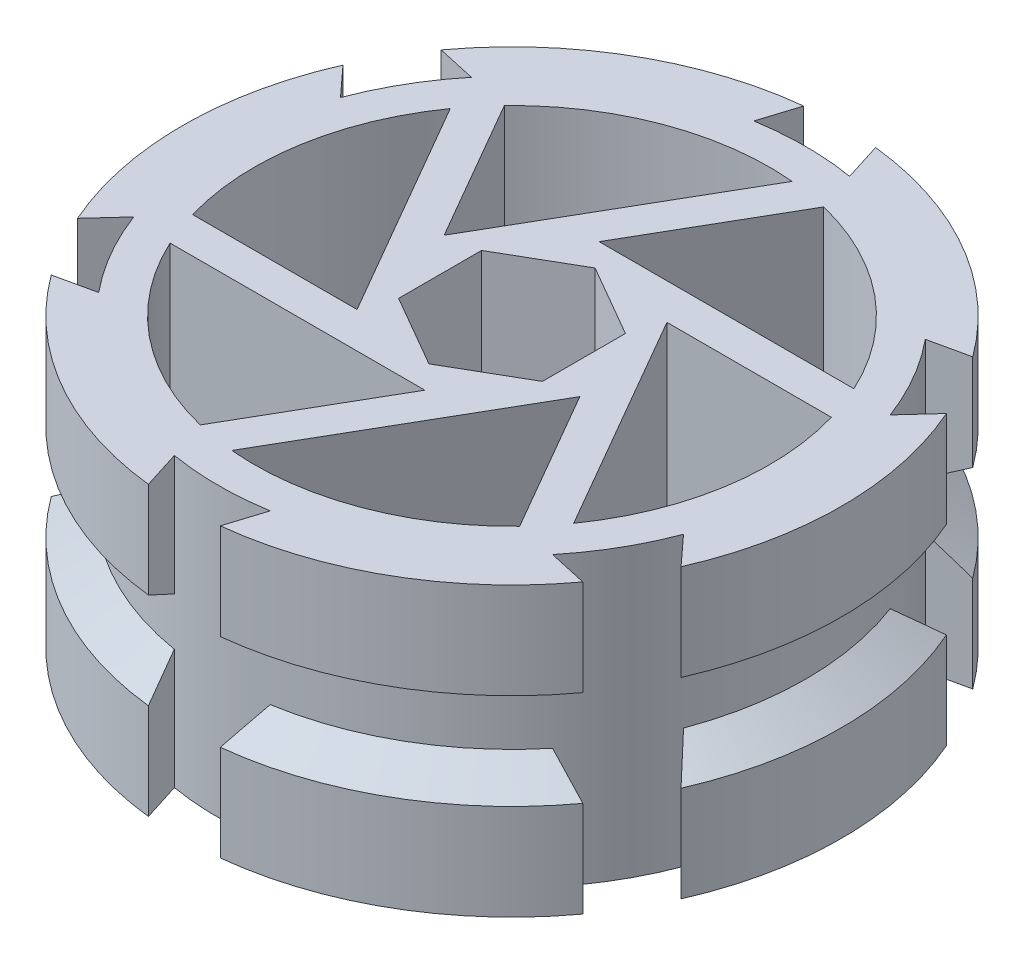
SolidWorks part; units mm, degrees
ref_plane "Front Plane" through (0, 0, 0) normal (0, 0, 1) x (1, 0, 0)
ref_plane "Top Plane" through (0, 0, 0) normal (0, 1, 0) x (1, 0, 0)
ref_plane "Right Plane" through (0, 0, 0) normal (1, 0, 0) x (0, 0, -1)
sketch "Sketch1" plane through (0, 0, 0) normal (0, 1, 0) x (1, 0, 0)
  circle A0 centre (0, 0) radius 27.5
  dimension "D1" = 55
extrude "Boss-Extrude1" add sketch "Sketch1" along normal blind 24
sketch "Sketch2" plane through (0, 0, 0) normal (0, 1, 0) x (1, 0, 0)
  line L0 (-4, 24.1713) -> (-3, 27.3359)
  line L1 (-3, 27.3359) -> (3, 27.3359) construction
  line L2 (3, 27.3359) -> (4, 24.1713)
  line L3 (0, 0) -> (0, 28.9493) construction
  line L4 (-4, 24.1713) -> (4, 24.1713) construction
  circle A1 centre (0, 0) radius 27.5 construction
  circle A2 centre (0, 0) radius 27.5
  circle A3 centre (0, 0) radius 24.5
  point P10 (0, 24.1713)
  point P12 (0, 27.3359)
  dimension "D3" = 3
  dimension "D1" = 6
  dimension "D2" = 8
extrude "Cut-Extrude3" cut sketch "Sketch2" against normal blind 2 and the other way through all contours L2 A2 L0 region at (0, 0, -25.8467)
pattern_circular "CirPattern1" count 6 over 360 about axis through (0, 24, 0) along (0, -1, 0) of "Cut-Extrude3"
sketch "Sketch3" plane through (0, 0, 0) normal (0, 1, 0) x (1, 0, 0)
  line L0 (5.1962, 9) -> (19.5256, 9)
  line L1 (3.4641, 6) -> (-3.4641, 6) construction
  line L2 (-3.4641, 6) -> (-6.9282, 0) construction
  line L3 (0, 0) -> (12.167, 21.0739) construction
  line L4 (-6.9282, 0) -> (-3.4641, -6) construction
  line L5 (-3.4641, -6) -> (3.4641, -6) construction
  line L6 (3.4641, -6) -> (6.9282, 0) construction
  line L7 (6.9282, 0) -> (3.4641, 6) construction
  line L9 (-6.9282, 0) -> (5.1268, 20.8798)
  line L11 (5.1962, 9) -> (-5.1962, 9)
  line L12 (-5.1962, 9) -> (-10.3923, 0)
  line L13 (-10.3923, 0) -> (-5.1962, -9)
  line L14 (-5.1962, -9) -> (5.1962, -9)
  line L15 (5.1962, -9) -> (10.3923, 0)
  line L16 (10.3923, 0) -> (5.1962, 9)
  circle A0 centre (0, 0) radius 21.5
  arc A2 (22.1736, 16.266) -> (3, 27.3359) centre (0, 0) ccw construction
  circle A8 centre (0, 0) radius 24.5 construction
  arc A9 (4, 24.1713) -> (-4, 24.1713) centre (0, 0) ccw construction
  circle A10 centre (0, 0) radius 6 construction
  circle A11 centre (0, 0) radius 9 construction
  point P16 (13.75, 23.8157)
  dimension "D1" = 3
  dimension "D2" = 3
  dimension "D3" = 12
extrude "Cut-Extrude4" cut sketch "Sketch3" along normal up to surface (24 mm away) contours L3 A0 region at (8.556, 0, -13.4223) up to face at (0, 24, 0)
sketch "Sketch5" plane through (0, 24, 0) normal (0, 1, 0) x (1, 0, 0)
  line L1 (0, 6.9282) -> (-6, 3.4641)
  line L2 (-6, 3.4641) -> (-6, -3.4641)
  line L3 (-6, -3.4641) -> (0, -6.9282)
  line L4 (0, -6.9282) -> (6, -3.4641)
  line L5 (6, -3.4641) -> (6, 3.4641)
  line L6 (6, 3.4641) -> (0, 6.9282)
  circle A0 centre (0, 0) radius 6 construction
  dimension "D1" = 12
pattern_circular "CirPattern2" count 6 over 360 about axis through (0, 24, 0) along (0, -1, 0) of "Cut-Extrude4" reverse direction yes
extrude "Cut-Extrude5" cut sketch "Sketch5" against normal blind 8.8
sketch "Sketch6" plane through (0, 0, 0) normal (0, 1, 0) x (1, 0, 0)
  circle A0 centre (0, 0) radius 1.9
  dimension "D1" = 3.8
extrude "Cut-Extrude6" cut sketch "Sketch6" along normal up to surface (24 mm away) up to face at (0, 24, 0)
ref_plane "Plane1" through (0, 12, 0) normal (0, 1, 0) x (1, 0, 0)
mirror "Mirror1" about plane through (0, 12, 0) normal (0, 1, 0) of "Cut-Extrude5"
sketch "Sketch7" plane through (0, 0, 0) normal (0, 0, 1) x (1, 0, 0)
  line L0 (24.5, 12) -> (24.5, 14)
  line L1 (30.0695, 12) -> (-30.0695, 12) construction
  line L2 (24.5, 14) -> (27.5, 16)
  line L3 (27.5, 0) -> (27.5, 24) construction
  line L4 (27.5, 16) -> (27.5, 12)
  line L5 (27.5, 12) -> (24.5, 12)
  line L6 (27.5, 24) -> (25.1736, 24) construction
  dimension "D1" = 2
  dimension "D2" = 8
  dimension "D3" = 3
ref_axis "Axis1" through (0, 24, 0) along (0, -1, 0)
revolve "Cut-Revolve1" cut sketch "Sketch7" angle 360 about axis through (0, 24, 0) along (0, -1, 0)
mirror "Mirror2" about plane through (0, 12, 0) normal (0, 1, 0) of "Cut-Revolve1"
